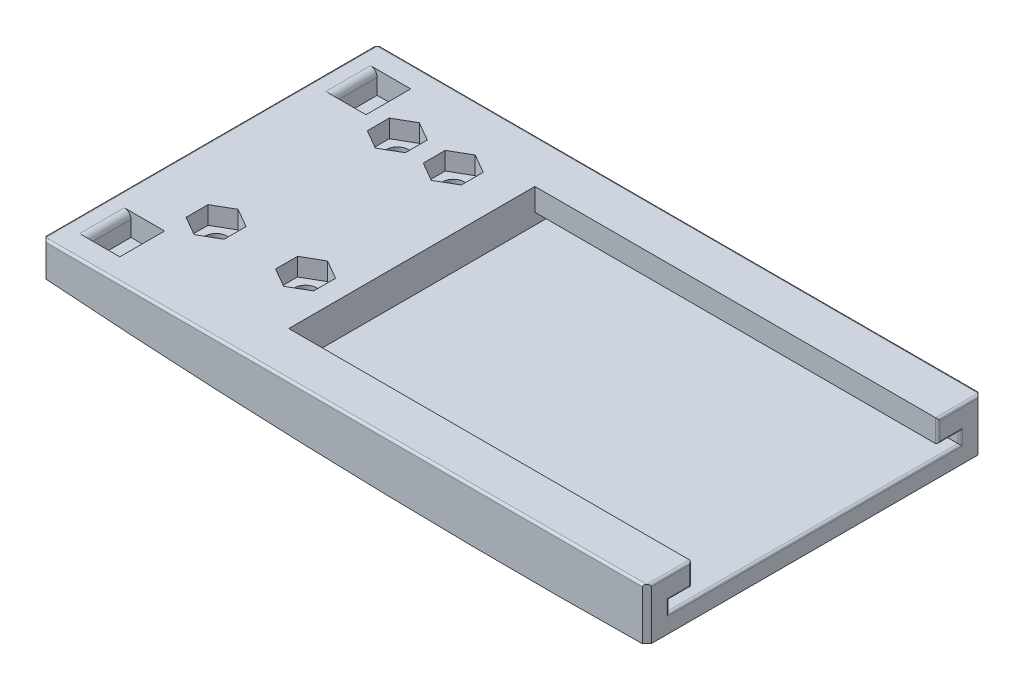
SolidWorks part; units mm, degrees
ref_plane "Front Plane" through (0, 0, 0) normal (0, 0, 1) x (1, 0, 0)
ref_plane "Top Plane" through (0, 0, 0) normal (0, 1, 0) x (1, 0, 0)
ref_plane "Right Plane" through (0, 0, 0) normal (1, 0, 0) x (0, 0, -1)
sketch "Sketch1" plane through (0, 0, 0) normal (0, 1, 0) x (1, 0, 0)
  line L1 (0, 0) -> (270.5, 0)
  line L2 (0, 0) -> (0, 150)
  line L3 (0, 150) -> (270.5, 150)
  line L4 (270.5, 0) -> (270.5, 150)
  dimension "D1" = 270.5
  dimension "D2" = 150
extrude "Boss-Extrude1" add sketch "Sketch1" along normal blind 15
sketch "Sketch5" plane through (0, 15, 0) normal (0, 1, 0) x (1, 0, 0)
  line L0 (0, 75) -> (90.5, 75) construction
  line L1 (0, 150) -> (0, 0) construction
  line L3 (33, 75) -> (33, 45) construction
  line L4 (40, 75) -> (40, 119) construction
  line L5 (65, 75) -> (65, 119) construction
  line L6 (73, 75) -> (73, 45) construction
  circle A1 centre (33, 45) radius 5
  circle A2 centre (40, 119) radius 5
  circle A3 centre (65, 119) radius 5
  circle A4 centre (73, 45) radius 5
  dimension "D1" = 33
  dimension "D9" = 10
  dimension "D10" = 10
  dimension "D11" = 10
  dimension "D12" = 10
  dimension "D2" = 30
  dimension "D3" = 40
  dimension "D4" = 44
  dimension "D5" = 65
  dimension "D6" = 44
  dimension "D7" = 73
  dimension "D8" = 30
ref_plane "Plane1" through (0, 0, -150) normal (0, 0, 1) x (1, 0, 0)
sketch "Sketch12" plane through (0, 0, -150) normal (0, 0, 1) x (1, 0, 0)
  line L3 (0, 0) -> (270.5, 0) construction
  line L5 (0, 0) -> (270.5, 0) construction
  line L8 (270.5, 0) -> (270.5, -7.957)
  line L9 (0, 0) -> (270.5, 0)
  arc A6 (0, 0) -> (270.5, -7.957) centre (222.5, 2962.1089) ccw
extrude "Boss-Extrude5" add sketch "Sketch12" along normal blind 150
extrude "Cut-Extrude7" cut sketch "Sketch5" against normal through all and the other way through all
sketch "Sketch13" plane through (0, 15, 0) normal (0, 1, 0) x (1, 0, 0)
  line L13 (40, 109.185) -> (48.5, 114.0925)
  line L14 (48.5, 114.0925) -> (48.5, 123.9075)
  line L15 (48.5, 123.9075) -> (40, 128.815)
  line L16 (40, 128.815) -> (31.5, 123.9075)
  line L17 (31.5, 123.9075) -> (31.5, 114.0925)
  line L18 (31.5, 114.0925) -> (40, 109.185)
  line L19 (65, 109.185) -> (73.5, 114.0925)
  line L20 (73.5, 114.0925) -> (73.5, 123.9075)
  line L21 (73.5, 123.9075) -> (65, 128.815)
  line L22 (65, 128.815) -> (56.5, 123.9075)
  line L23 (56.5, 123.9075) -> (56.5, 114.0925)
  line L24 (56.5, 114.0925) -> (65, 109.185)
  line L25 (33, 35.185) -> (41.5, 40.0925)
  line L26 (41.5, 40.0925) -> (41.5, 49.9075)
  line L27 (41.5, 49.9075) -> (33, 54.815)
  line L28 (33, 54.815) -> (24.5, 49.9075)
  line L29 (24.5, 49.9075) -> (24.5, 40.0925)
  line L30 (24.5, 40.0925) -> (33, 35.185)
  line L31 (73, 35.185) -> (81.5, 40.0925)
  line L32 (81.5, 40.0925) -> (81.5, 49.9075)
  line L33 (81.5, 49.9075) -> (73, 54.815)
  line L34 (73, 54.815) -> (64.5, 49.9075)
  line L35 (64.5, 49.9075) -> (64.5, 40.0925)
  line L36 (64.5, 40.0925) -> (73, 35.185)
  circle A0 centre (40, 119) radius 8.5 construction
  circle A1 centre (40, 119) radius 5 construction
  circle A2 centre (65, 119) radius 8.5 construction
  circle A3 centre (65, 119) radius 5 construction
  circle A4 centre (33, 45) radius 8.5 construction
  circle A5 centre (33, 45) radius 5 construction
  circle A6 centre (73, 45) radius 8.5 construction
  circle A7 centre (73, 45) radius 5 construction
extrude "Cut-Extrude8" cut sketch "Sketch13" against normal blind 8
sketch "Sketch15" plane through (270.5, 0, 0) normal (1, 0, 0) x (0, 0, -1)
  line L1 (20, 15) -> (130, 15)
  line L2 (10, 5) -> (10, 0)
  line L3 (10, 0) -> (140, 0)
  line L4 (140, 5) -> (140, 0)
  line L5 (0, 15) -> (0, -7.957) construction
  line L6 (10, 5) -> (20, 5)
  line L9 (20, 5) -> (20, 15)
  line L10 (140, 5) -> (130, 5)
  line L13 (130, 5) -> (130, 15)
  dimension "D1" = 10
  dimension "D2" = 130
  dimension "D3" = 10
  dimension "D4" = 10
  dimension "D5" = 10
  dimension "D6" = 10
  dimension "D7" = 5
extrude "Cut-Extrude9" cut sketch "Sketch15" against normal blind 180
chamfer "Chamfer1" distance 2 angle 45 4 edges at (270.5, 3.5215, 0) (270.5, 3.5215, -150) (0, 7.5, -150) (0, 7.5, 0)
sketch "Sketch16" plane through (0, 15, 0) normal (0, 1, 0) x (1, 0, 0)
  line L0 (10, 30) -> (25, 30)
  line L1 (10, 140) -> (25, 140)
  line L2 (10, 140) -> (10, 120)
  line L3 (10, 120) -> (25, 120)
  line L4 (25, 140) -> (25, 120)
  line L5 (10, 30) -> (10, 10)
  line L6 (10, 10) -> (25, 10)
  line L7 (25, 30) -> (25, 10)
  line L8 (0, 148) -> (0, 2) construction
  line L9 (268.5, 150) -> (2, 150) construction
  line L10 (2, 0) -> (268.5, 0) construction
  dimension "D1" = 15
  dimension "D2" = 20
  dimension "D3" = 10
  dimension "D4" = 10
  dimension "D5" = 15
  dimension "D6" = 20
  dimension "D7" = 10
  dimension "D8" = 10
extrude "Cut-Extrude10" cut sketch "Sketch16" against normal blind 10
fillet "Fillet2" radius 1 12 edges at (270.5, 15, -139) (270.5, 10, -130) (270.5, 5, -135) (270.5, 2.5, -140) (270.5, 0, -75) (270.5, 2.5, -10) (270.5, 5, -15) (270.5, 10, -20) (270.5, 15, -11) (135.25, 15, -150) (135.25, 15, 0) (0, 15, -75)
fillet "Fillet3" radius 3 2 edges at (10, 15, -130) (10, 15, -20)
